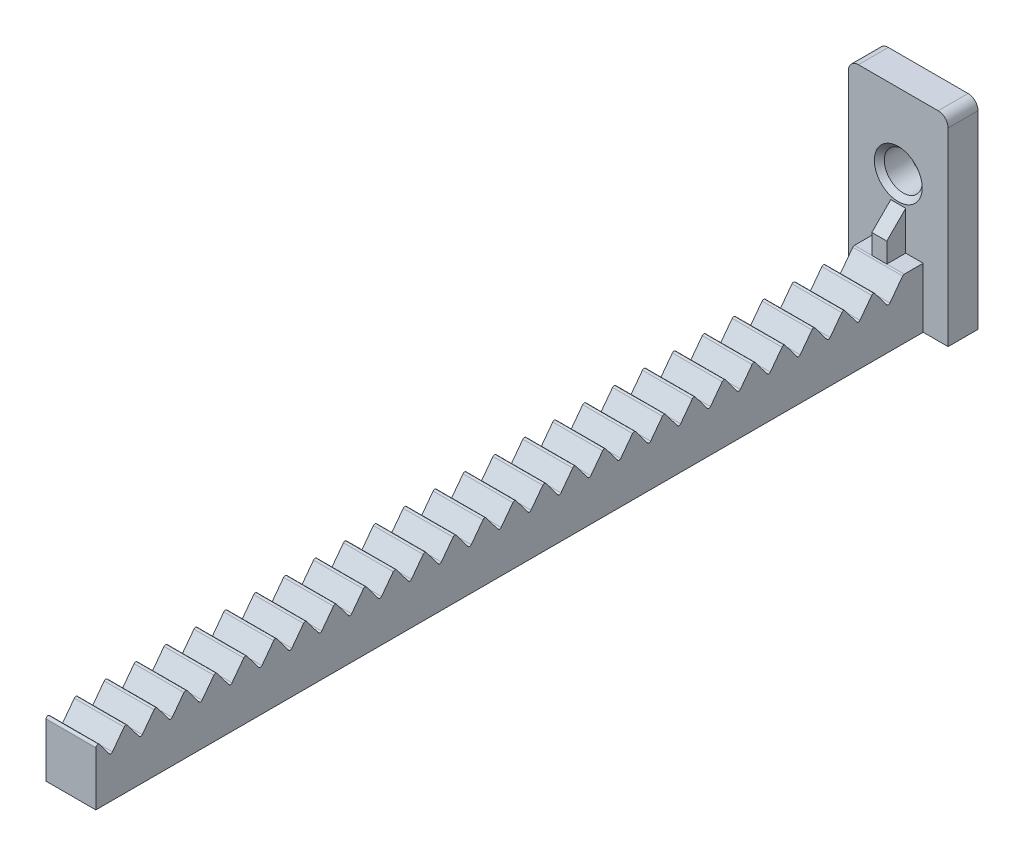
SolidWorks part; units mm, degrees
ref_plane "Plan de face" through (0, 0, 0) normal (0, 0, 1) x (1, 0, 0)
ref_plane "Plan de dessus" through (0, 0, 0) normal (0, 1, 0) x (1, 0, 0)
ref_plane "Plan de droite" through (0, 0, 0) normal (1, 0, 0) x (0, 0, -1)
sketch "Esquisse1" plane through (0, 0, 0) normal (1, 0, 0) x (0, 0, -1)
  line L1 (-41.5, -3) -> (41.5, -3)
  line L2 (-41.5, -3) -> (-41.5, 3)
  line L3 (-41.5, 3) -> (41.5, 3)
  line L4 (41.5, -3) -> (41.5, 3)
  line L5 (-41.5, -3) -> (41.5, 3) construction
  line L6 (-41.5, 3) -> (41.5, -3) construction
  point P0 (0, 0)
  dimension "D1" = 6
  dimension "D2" = 83
extrude "Boss.-Extru.1" add sketch "Esquisse1" along normal blind 5
sketch "Esquisse2" plane through (5, 0, 0) normal (1, 0, 0) x (0, 0, -1)
  line L0 (-41.5, 3) -> (-38.5, 3) construction
  line L1 (41.5, 3) -> (-41.5, 3) construction
  line L2 (-38.5, 3) -> (-35.5, 3) construction
  line L3 (-35.5, 3) -> (-32.5, 3) construction
  line L5 (-40, 3) -> (-40, 1) construction
  line L6 (-37, 3) -> (-37, 1) construction
  line L7 (-34, 3) -> (-34, 1) construction
  line L9 (-41.5, 3) -> (-40, 1)
  line L10 (-40, 1) -> (-38.5, 3)
  line L11 (-38.5, 3) -> (-37, 1)
  line L12 (-37, 1) -> (-35.5, 3)
  line L13 (-35.5, 3) -> (-34, 1)
  line L14 (-34, 1) -> (-32.5, 3)
  line L15 (-41.5, 3) -> (-32.5, 3)
  line M10 (41.5, 3) -> (-41.5, 3)
  dimension "D1" = 3
  dimension "D2" = 3
  dimension "D3" = 3
  dimension "D5" = 2
  dimension "D6" = 2
  dimension "D7" = 2
extrude "Enlèv. mat.-Extru.1" cut sketch "Esquisse2" against normal blind 5 contours L9 L10 M10 | L11 L12 M10 | L13 L14 M10 region at (5, 2.3333, 40) region at (5, 2.3333, 34) region at (5, 2.3333, 37)
fillet "Congé1" radius 0.2 5 edges at (2.5, 1, 34) (2.5, 3, 35.5) (2.5, 1, 37) (2.5, 3, 38.5) (2.5, 1, 40)
pattern_linear "Répétition linéaire4" count 9 spacing 9 along (0, 0, -1) of "Enlèv. mat.-Extru.1", "Congé1"
fillet "Congé2" radius 0.2 10 edges at (2.5, 3, -3.5) (2.5, 3, 5.5) (2.5, 3, 14.5) (2.5, 3, 23.5) (2.5, 3, 32.5) (2.5, 3, 41.5) (2.5, 3, -39.5) (2.5, 3, -30.5) (2.5, 3, -21.5) (2.5, 3, -12.5)
sketch "Esquisse3" plane through (0, 0, -41.5) normal (0, 0, -1) x (-1, 0, 0)
  line L0 (-5, 3) -> (0, -3) construction
  line L2 (-7.5, 3) -> (2.5, 3)
  line L3 (-7.5, 3) -> (-7.5, -3)
  line L4 (-7.5, -3) -> (2.5, -3)
  line L5 (2.5, 3) -> (2.5, -3)
  line L6 (-7.5, 3) -> (2.5, -3) construction
  line L7 (-7.5, -3) -> (2.5, 3) construction
  point P4 (-2.5, 0)
  dimension "D1" = 10
  dimension "D2" = 6
extrude "Boss.-Extru.2" add sketch "Esquisse3" along normal blind 3
sketch "Esquisse4" plane through (0, 3, 0) normal (0, 1, 0) x (1, 0, 0)
  line L0 (-2.5, 44.5) -> (7.5, 41.5) construction
  line L2 (-2.5, 41.5) -> (7.5, 41.5)
  line L3 (-2.5, 41.5) -> (-2.5, 44.5)
  line L4 (-2.5, 44.5) -> (7.5, 44.5)
  line L5 (7.5, 41.5) -> (7.5, 44.5)
  line L6 (-2.5, 41.5) -> (7.5, 44.5) construction
  line L7 (-2.5, 44.5) -> (7.5, 41.5) construction
  point P4 (2.5, 43)
extrude "Boss.-Extru.3" add sketch "Esquisse4" along normal blind 14
sketch "Esquisse5" plane through (0, 0, -44.5) normal (0, 0, -1) x (-1, 0, 0)
  line L0 (-2.5, -3) -> (-2.5, 9.5) construction
  line L1 (-7.5, -3) -> (2.5, -3) construction
  circle A0 centre (-2.5, 9.5) radius 1.9
  dimension "D2" = 3.8
  dimension "D1" = 12.5
extrude "Enlèv. mat.-Extru.2" cut sketch "Esquisse5" against normal blind 15
fillet "Congé3" radius 1 2 edges at (-2.5, 17, -43) (7.5, 17, -43)
chamfer "Chanfrein1" distance 0.5 angle 45 1 edges at (0.6, 9.5, -41.5)
sketch "Esquisse6" plane through (0, 3, 0) normal (0, 1, 0) x (1, 0, 0)
  line L0 (2.5, 41.5) -> (2.5, 39.6) construction
  line L1 (-1.5, 41.5) -> (6.5, 41.5) construction
  line L2 (0, 39.6) -> (5, 39.6) construction
  line L3 (0, 41.5) -> (5, 41.5) construction
  line L4 (1.75, 39.6) -> (3.25, 39.6)
  line L5 (1.75, 39.6) -> (1.75, 41.5)
  line L6 (1.75, 41.5) -> (3.25, 41.5)
  line L7 (3.25, 39.6) -> (3.25, 41.5)
  line L8 (1.75, 39.6) -> (3.25, 41.5) construction
  line L9 (1.75, 41.5) -> (3.25, 39.6) construction
  point P6 (2.5, 40.55)
  dimension "D1" = 1.5
extrude "Boss.-Extru.4" add sketch "Esquisse6" along normal blind 4
chamfer "Chanfrein2" distance 2 angle 45 1 edges at (2.5, 7, -39.6)
